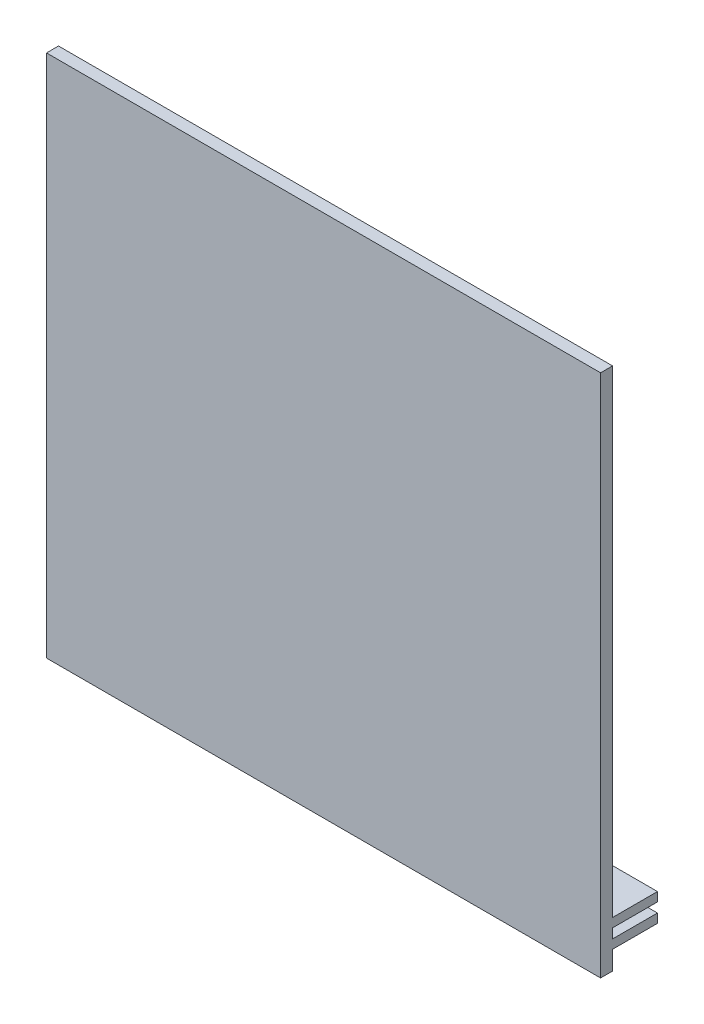
SolidWorks part; units mm, degrees
ref_plane "前基準面" through (0, 0, 0) normal (0, 0, 1) x (1, 0, 0)
ref_plane "上基準面" through (0, 0, 0) normal (0, 1, 0) x (1, 0, 0)
ref_plane "右基準面" through (0, 0, 0) normal (1, 0, 0) x (0, 0, -1)
sketch "草圖1" plane through (0, 0, 0) normal (0, 0, 1) x (1, 0, 0)
  line L1 (-71.1335, 108.4737) -> (113.8665, 108.4737)
  line L2 (-71.1335, 108.4737) -> (-71.1335, -66.5263)
  line L3 (-71.1335, -66.5263) -> (113.8665, -66.5263)
  line L4 (113.8665, 108.4737) -> (113.8665, -66.5263)
  dimension "D1" = 185
  dimension "D2" = 175
extrude "填料-伸長1" add sketch "草圖1" along normal blind 4
sketch "草圖2" plane through (0, 0, 0) normal (0, 0, -1) x (-1, 0, 0)
  line L0 (71.1335, 108.4737) -> (71.1335, -66.5263) construction
  line L1 (71.1335, -54.1263) -> (-68.8665, -54.1263)
  line L2 (71.1335, -54.1263) -> (71.1335, -57.1263)
  line L3 (71.1335, -57.1263) -> (-68.8665, -57.1263)
  line L4 (-68.8665, -54.1263) -> (-68.8665, -57.1263)
  line L5 (-95.4909, -54.0263) -> (-51.1617, -54.0263) construction
  line L6 (71.1335, -50.9263) -> (-68.8665, -50.9263)
  line L7 (71.1335, -50.9263) -> (71.1335, -47.9263)
  line L8 (71.1335, -47.9263) -> (-68.8665, -47.9263)
  line L9 (-68.8665, -50.9263) -> (-68.8665, -47.9263)
  line L10 (-43.7374, -51.0263) -> (-93.6544, -51.0263) construction
  dimension "D1" = 140
  dimension "D2" = 140
  dimension "D3" = 0.1
  dimension "D4" = 3
  dimension "D5" = 0.1
  dimension "D6" = 3
extrude "填料-伸長2" add sketch "草圖2" along normal blind 15
sketch "草圖3" plane through (0, -57.1263, 0) normal (0, -1, 0) x (1, 0, 0)
  line L0 (-65.1335, -10) -> (62.8665, -10) construction
  line L1 (-65.1335, -8.4) -> (62.8665, -8.4)
  line L2 (-65.1335, -11.6) -> (62.8665, -11.6)
  line L3 (68.8665, 0) -> (-71.1335, 0) construction
  line L4 (-71.1335, -15) -> (-71.1335, 0) construction
  line L5 (68.8665, -15) -> (68.8665, 0) construction
  arc A0 (-65.1335, -8.4) -> (-65.1335, -11.6) centre (-65.1335, -10) ccw
  arc A1 (62.8665, -11.6) -> (62.8665, -8.4) centre (62.8665, -10) ccw
  point P2 (-1.1335, -10)
  point P13 (0, 0)
  dimension "D2" = 6
  dimension "D1" = 10
  dimension "D3" = 6
  dimension "D4" = 3.2
extrude "除料-伸長1" cut sketch "草圖3" against normal up to surface (9.2 mm away) up to face at (-1.1335, -47.9263, -7.5)
sketch "草圖4" plane through (0, 0, 0) normal (0, 0, -1) x (-1, 0, 0)
  line L0 (-68.8665, -54.0263) -> (-68.8665, -51.0263)
  line L1 (-68.8665, -54.0263) -> (-113.8665, -54.0263)
  line L2 (-68.8665, -51.0263) -> (-113.8665, -51.0263)
  line L3 (-113.8665, -54.0263) -> (-113.8665, -51.0263)
  line L4 (-68.8665, -57.2263) -> (-113.8665, -57.2263)
  line L5 (-68.8665, -57.2263) -> (-68.8665, -60.2263)
  line L6 (-113.8665, -57.2263) -> (-113.8665, -60.2263)
  line L7 (-68.8665, -60.2263) -> (-113.8665, -60.2263)
  line L10 (-113.8665, -66.5263) -> (-113.8665, 108.4737) construction
  line L20 (71.1335, -54.1263) -> (-68.8665, -54.1263) construction
  line L21 (-68.8665, -57.1263) -> (71.1335, -57.1263) construction
  line L22 (-68.8665, -50.9263) -> (71.1335, -50.9263) construction
  point P0 (0, 0)
  point P16 (0, 0)
  dimension "D1" = 3
  dimension "D2" = 0.1
  dimension "D3" = 0.1
  dimension "D4" = 0.1
extrude "填料-伸長5" add sketch "草圖4" along normal blind 15
sketch "草圖5" plane through (0, -60.2263, 0) normal (0, -1, 0) x (1, 0, 0)
  line L2 (113.8665, -15) -> (113.8665, 0) construction
  line L3 (113.8665, -15) -> (68.8665, -15) construction
  circle A0 centre (97.3665, -10) radius 1.6
  dimension "D1" = 3.2
  dimension "D2" = 16.5
  dimension "D3" = 5
extrude "除料-伸長2" cut sketch "草圖5" against normal up to surface (9.2 mm away) up to face at (91.3665, -51.0263, -7.5)
